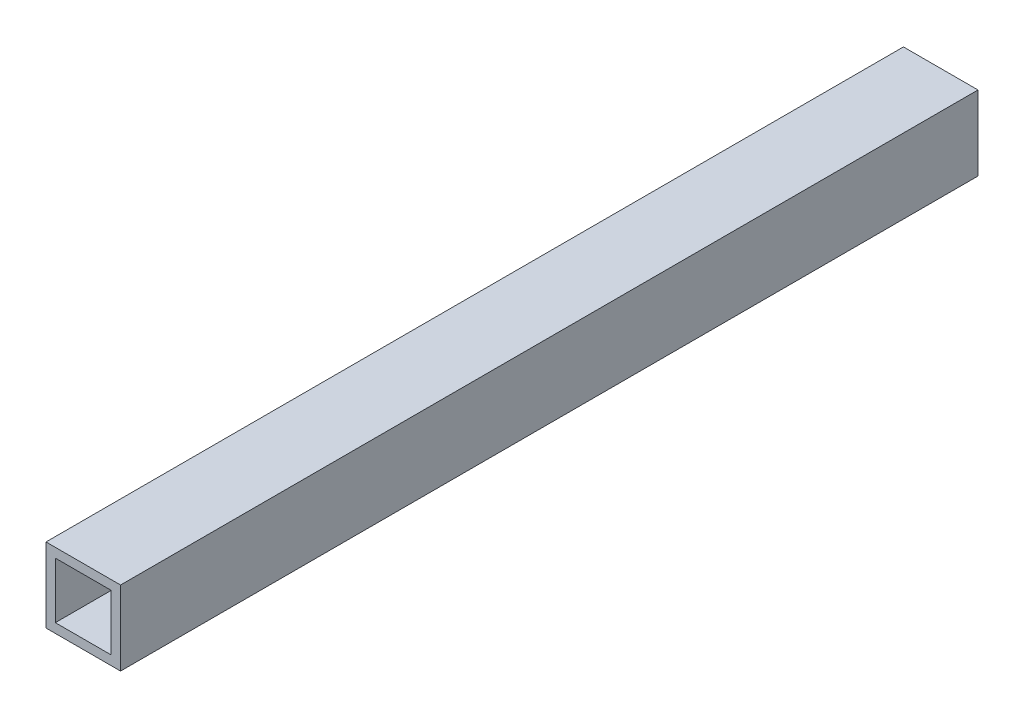
SolidWorks part; units mm, degrees
material "6061 Alloy"
ref_plane "Front Plane" through (0, 0, 0) normal (0, 0, 1) x (1, 0, 0)
ref_plane "Top Plane" through (0, 0, 0) normal (0, 1, 0) x (1, 0, 0)
ref_plane "Right Plane" through (0, 0, 0) normal (1, 0, 0) x (0, 0, -1)
sketch "Sketch1" plane through (0, 0, 0) normal (0, 0, 1) x (1, 0, 0)
  line L0 (12.7, 0) -> (9.525, 0) construction
  line L1 (-12.7, 0) -> (12.7, 0) construction
  line L2 (0, 12.7) -> (0, -12.7)
  point P7 (0, 0)
sketch "Sketch2" plane through (0, 0, 0) normal (1, 0, 0) x (0, 0, -1)
  line L0 (146.05, 0) -> (-146.05, 0)
  point P4 (0, 0)
  dimension "Length" = 292.1
sketch "Sketch3" plane through (0, 0, 0) normal (0, 0, 1) x (1, 0, 0)
  line L0 (-12.7, 0) -> (12.7, 0) construction
  line L5 (12.7, -12.7) -> (-12.7, -12.7)
  line L6 (12.7, -12.7) -> (12.7, 12.7)
  line L11 (12.7, 12.7) -> (-12.7, 12.7)
  line L12 (-12.7, -12.7) -> (-12.7, 12.7)
  line L14 (12.7, -12.7) -> (-12.7, 12.7) construction
  line L15 (12.7, 12.7) -> (-12.7, -12.7) construction
  line L16 (9.525, -9.525) -> (-9.525, -9.525)
  line L17 (9.525, -9.525) -> (9.525, 9.525)
  line L18 (9.525, 9.525) -> (-9.525, 9.525)
  line L19 (-9.525, -9.525) -> (-9.525, 9.525)
  line L20 (9.525, -9.525) -> (-9.525, 9.525) construction
  line L21 (9.525, 9.525) -> (-9.525, -9.525) construction
  point P0 (0, 0)
  point P5 (0, 0)
  point P13 (9.525, -12.7)
  dimension "D1" = 3.175
extrude "Boss-Extrude1" add sketch "Sketch3" along normal up to vertex (146.05 mm away) and the other way up to vertex (146.05 mm away) up to point (0, 0, 146.05) other way up to point (0, 0, -146.05)
sketch "Sketch5" plane through (0, 0, 0) normal (1, 0, 0) x (0, 0, -1)
  line L0 (-146.05, 0) -> (146.05, 0) construction
  line L3 (-146.05, -12.7) -> (-146.05, 12.7) construction
  line L4 (146.05, -12.7) -> (146.05, 12.7) construction
  point P6 (-117.475, 0)
  point P7 (-107.95, 0)
  point P8 (107.95, 0)
  point P10 (117.475, 0)
  dimension "D1" = 28.575
  dimension "D2" = 38.1
  dimension "D3" = 28.575
  dimension "D4" = 38.1
equation "\"D1@Sketch3\"=\"Wall thickness@Sketch1\""
equation "\"D1@Sketch5\"=\"Width@Sketch1\"*1.125"
equation "\"D2@Sketch5\"=\"Width@Sketch1\"*1.5"
equation "\"D3@Sketch5\"=\"D1@Sketch5\""
equation "\"D4@Sketch5\"=\"D2@Sketch5\""
equation "\"D2@Sketch3\"=\"Wall Thickness@Sketch1\""
